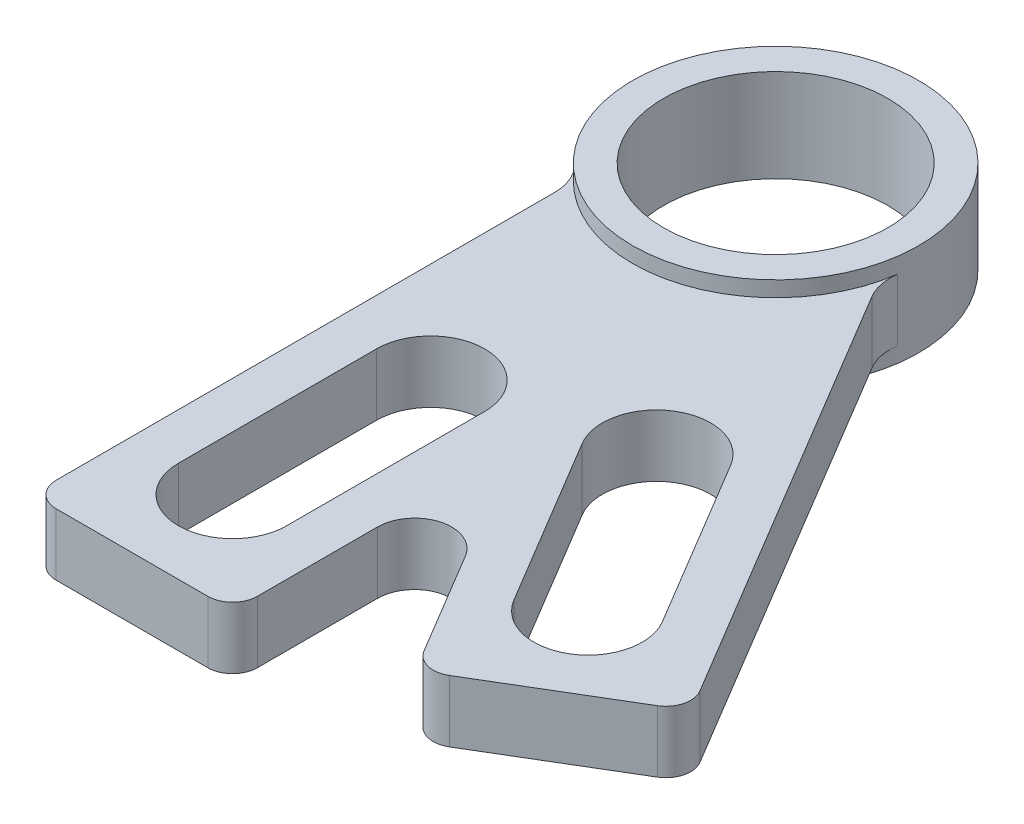
SolidWorks part; units mm, degrees
material "AISI 4130 Steel, normalized at 870C"
ref_plane "Front Plane" through (0, 0, 0) normal (0, 0, 1) x (1, 0, 0)
ref_plane "Top Plane" through (0, 0, 0) normal (0, 1, 0) x (1, 0, 0)
ref_plane "Right Plane" through (0, 0, 0) normal (1, 0, 0) x (0, 0, -1)
sketch "Sketch1" plane through (0, 0, 0) normal (0, 1, 0) x (1, 0, 0)
  line L0 (0, 0) -> (0, -66.04) construction
  line L1 (0, 0) -> (33.8815, -56.6862) construction
  line L2 (0, -55.7213) -> (0, -35.4013) construction
  line L3 (-5.5562, -55.7213) -> (-5.5562, -35.4013)
  line L4 (5.5563, -55.7213) -> (5.5563, -35.4013)
  line L5 (28.5876, -47.829) -> (18.1625, -30.3871) construction
  line L6 (23.8183, -50.6796) -> (13.3932, -33.2377)
  line L7 (33.3568, -44.9783) -> (22.9317, -27.5364)
  line L8 (0, -66.04) -> (0, -61.2775) construction
  line L9 (33.8815, -56.6862) -> (31.4382, -52.5982) construction
  line L10 (-10.3187, -66.04) -> (10.3188, -66.04)
  line L11 (25.0243, -61.9802) -> (42.7388, -51.3922)
  line L12 (-10.3187, -66.04) -> (-10.3187, -10.4432)
  line L13 (10.3188, -66.04) -> (10.3188, -37.3767)
  line L14 (42.7388, -51.3922) -> (14.2151, -3.6701)
  line L15 (25.0243, -61.9802) -> (10.3188, -37.3767)
  line L16 (188.8394, -315.9414) -> (17.7009, -29.6148) construction
  line L22 (0, 0) -> (10.3188, -37.3767) construction
  circle A0 centre (0, 0) radius 11.5062
  circle A1 centre (0, 0) radius 14.6812
  arc A2 (-5.5562, -55.7213) -> (5.5563, -55.7213) centre (0, -55.7213) ccw
  arc A3 (5.5563, -35.4013) -> (-5.5562, -35.4013) centre (0, -35.4013) ccw
  arc A4 (23.8183, -50.6796) -> (33.3568, -44.9783) centre (28.5876, -47.829) ccw
  arc A5 (22.9317, -27.5364) -> (13.3932, -33.2377) centre (18.1625, -30.3871) ccw
  point P8 (0, -45.5613)
  point P13 (23.375, -39.108)
  point P25 (0, -66.04)
  point P27 (33.8815, -56.6862)
  dimension "D2" = 29.3624
  dimension "D3" = 4.7625
  dimension "D4" = 4.7625
  dimension "D5" = 20.32
  dimension "D6" = 66.04
  dimension "D7" = 20.6375
extrude "Bearing_Insert_Extrude" add sketch "Sketch1" along normal mid plane 9.525 contours A1 A0 region at (-5.4988, 0, -13.1636)
extrude "Apex_Slot_Insert_Extrude" add sketch "Sketch1<4>" along normal mid plane 6.35 contours A1 L12 L10 L13 L15 L11 L14 A5 L7 A4 L6 A3 L4 A2 L3 | L13 L15 region at (9.9891, 0, 36.1827)
sketch "Sketch1<4>" plane through (0, 0, 0) normal (0, 1, 0) x (1, 0, 0) same geometry as "Sketch1"
fillet "Fillet1" radius 5.08 2 edges at (14.2151, 0, 3.6701) (-10.3187, 0, 10.4432)
fillet "Fillet2" radius 2.54 4 edges at (42.7388, 0, 51.3922) (25.0243, 0, 61.9802) (10.3188, 0, 66.04) (-10.3187, 0, 66.04)
fillet "Fillet3" radius 3.81 1 edges at (10.3188, 0, 37.3767)
equation "\"Apex_thickness\"= .25"
equation "\"Bearing_diameter\"= 0.906in"
equation "\"A-arm_angle\"= 39.1893"
equation "\"D1@Sketch1\"=\"Bearing_diameter\""
equation "\"D1@Apex_Slot_Insert_Extrude\"=\"Apex_thickness\""
